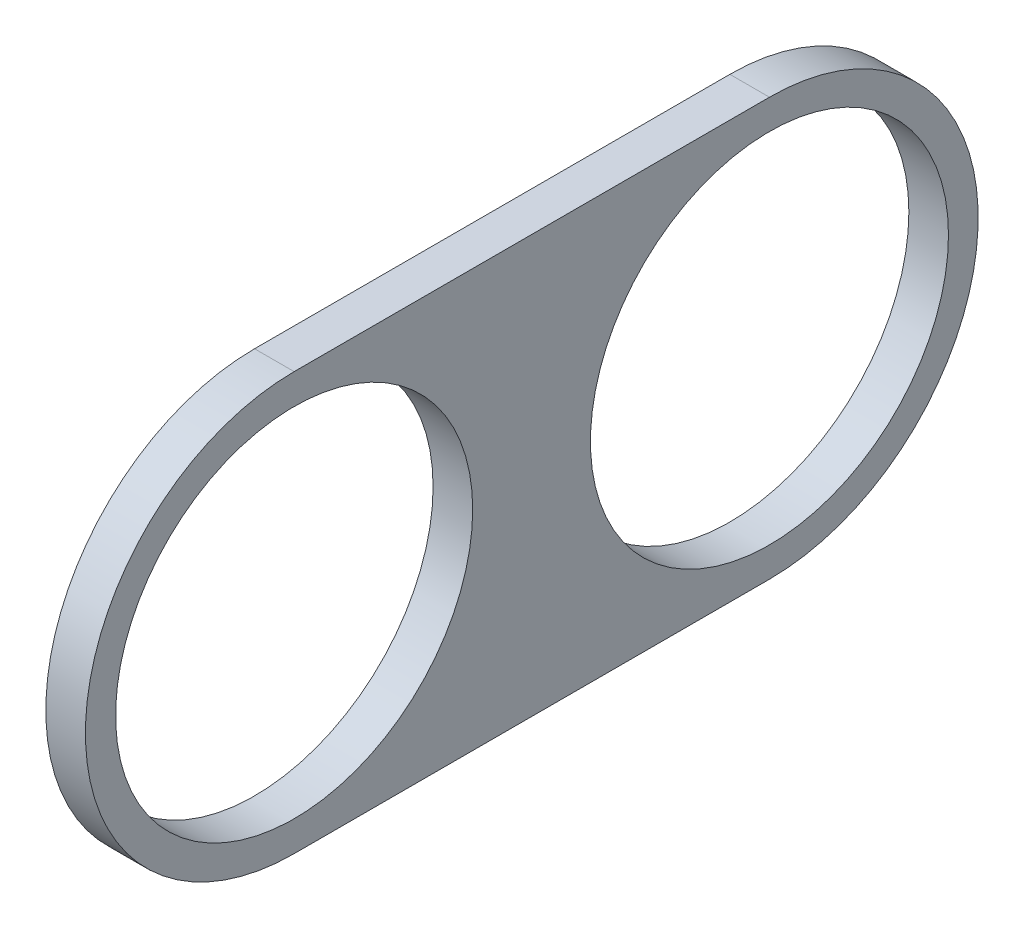
SolidWorks part; units mm, degrees
material "6061-T6 (SS)"
ref_plane "Front" through (0, 0, 0) normal (0, 0, 1) x (1, 0, 0)
ref_plane "Top" through (0, 0, 0) normal (0, 1, 0) x (1, 0, 0)
ref_plane "Right" through (0, 0, 0) normal (1, 0, 0) x (0, 0, -1)
sketch "Sketch1" plane through (0, 0, 0) normal (1, 0, 0) x (0, 0, -1)
  line L0 (-19.05, 0) -> (19.05, 0) construction
  line L1 (-19.05, 16.7323) -> (19.05, 16.7323)
  line L2 (-19.05, -16.7323) -> (19.05, -16.7323)
  arc A0 (-19.05, 16.7323) -> (-19.05, -16.7323) centre (-19.05, 0) ccw
  arc A1 (19.05, -16.7323) -> (19.05, 16.7323) centre (19.05, 0) ccw
  circle A2 centre (19.05, 0) radius 14.351
  circle A3 centre (-19.05, 0) radius 14.3129
  point P2 (0, 0)
  dimension "D1" = 2.3812
  dimension "D2" = 28.702
  dimension "D4" = 28.6258
  dimension "D3" = 38.1
extrude "Boss-Extrude1" add sketch "Sketch1" along normal blind 3.175
